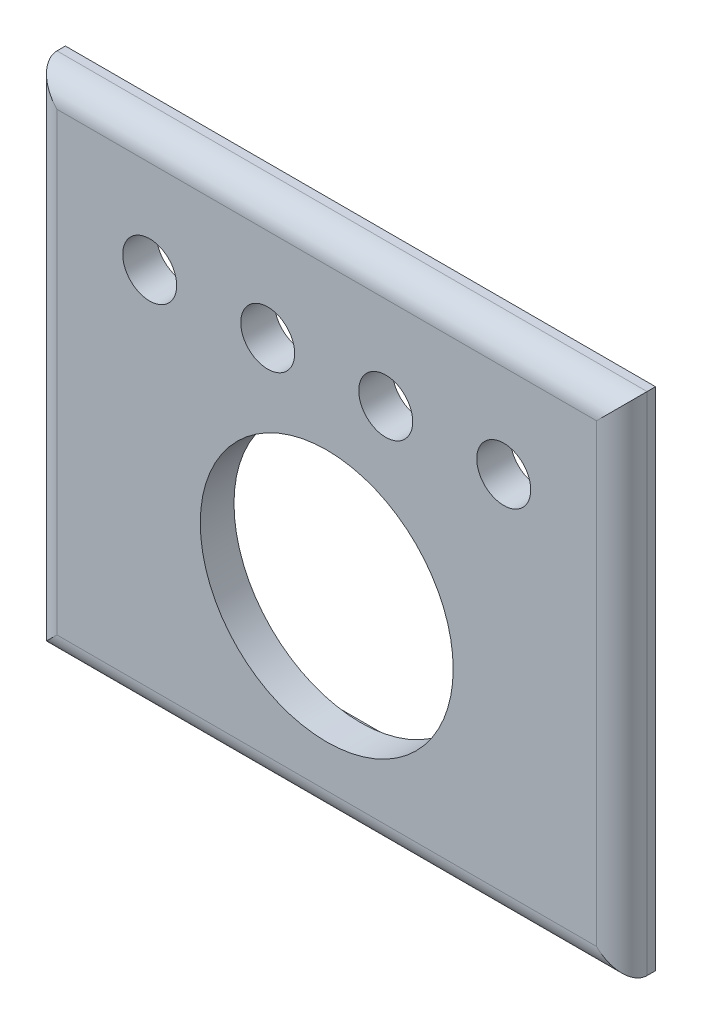
SolidWorks part; units mm, degrees
ref_plane "Спереди" through (0, 0, 0) normal (0, 0, 1) x (1, 0, 0)
ref_plane "Сверху" through (0, 0, 0) normal (0, 1, 0) x (1, 0, 0)
ref_plane "Справа" through (0, 0, 0) normal (1, 0, 0) x (0, 0, -1)
sketch "Sketch1" plane through (0, 0, 0) normal (0, 0, 1) x (1, 0, 0)
  line L1 (35, -30) -> (-35, -30)
  line L2 (35, -30) -> (35, 30)
  line L3 (35, 30) -> (-35, 30)
  line L4 (-35, -30) -> (-35, 30)
  line L5 (35, -30) -> (-35, 30) construction
  line L6 (35, 30) -> (-35, -30) construction
  point P0 (0, 0)
  dimension "D1" = 70
  dimension "D2" = 60
extrude "Boss-Extrude1" add sketch "Sketch1" along normal blind 4
sketch "Sketch2" plane through (0, 0, 0) normal (0, 0, -1) x (-1, 0, 0)
  line L0 (35, -30) -> (-35, -30) construction
  line L1 (-31.8, 26.8) -> (31.8, 26.8)
  line L2 (-31.8, 26.8) -> (-31.8, -26.8)
  line L3 (-31.8, -26.8) -> (31.8, -26.8)
  line L4 (31.8, 26.8) -> (31.8, -26.8)
  line L5 (-31.8, 26.8) -> (31.8, -26.8) construction
  line L6 (-31.8, -26.8) -> (31.8, 26.8) construction
  line L7 (-35, -30) -> (-35, 30) construction
  line L9 (28.8, -23.8) -> (-28.8, -23.8)
  line L10 (28.8, -23.8) -> (28.8, 23.8)
  line L11 (28.8, 23.8) -> (-28.8, 23.8)
  line L12 (-28.8, -23.8) -> (-28.8, 23.8)
  line L13 (28.8, -23.8) -> (-28.8, 23.8) construction
  line L14 (28.8, 23.8) -> (-28.8, -23.8) construction
  point P0 (0, 0)
  point P10 (0, 0)
  dimension "D1" = 3.2
  dimension "D2" = 3.2
  dimension "D3" = 3
  dimension "D4" = 3
extrude "Boss-Extrude2" add sketch "Sketch2" along normal blind 2
chamfer "Chamfer1" distance 0.5 angle 70 4 edges at (-31.8, 0, -2) (0, 26.8, -2) (31.8, 0, -2) (0, -26.8, -2) first distance on face at (0, 0, -2)
fillet "Fillet1" radius 3 4 edges at (0, 30, 4) (35, 0, 4) (0, -30, 4) (-35, 0, 4)
sketch "Sketch3" plane through (0, 0, 4) normal (0, 0, 1) x (1, 0, 0)
  line L0 (0, -41.7208) -> (0, 41.7208) construction
  line L1 (22.303, 16) -> (-22.303, 16) construction
  line L2 (21.3031, 11.2919) -> (-21.3031, 11.2919) construction
  circle A0 centre (-21, 16) radius 3.2
  circle A1 centre (-7, 16) radius 3.2
  circle A2 centre (7, 16) radius 3.2
  circle A3 centre (21, 16) radius 3.2
  point P4 (0, 0)
  point P7 (0, 16)
  point P10 (0, 11.2919)
  dimension "D1" = 6.4
  dimension "D2" = 16
  dimension "D3" = 14
  dimension "D4" = 14
  dimension "D5" = 14
  dimension "D6" = 7
extrude "Cut-Extrude1" cut sketch "Sketch3" against normal through all
sketch "Sketch4" plane through (0, 0, 4) normal (0, 0, 1) x (1, 0, 0)
  line L0 (0, -40.1993) -> (0, 40.1993) construction
  circle A0 centre (0, -7) radius 15
  point P3 (0, 0)
  dimension "D1" = 30
  dimension "D2" = 7
extrude "Cut-Extrude2" cut sketch "Sketch4" against normal through all
